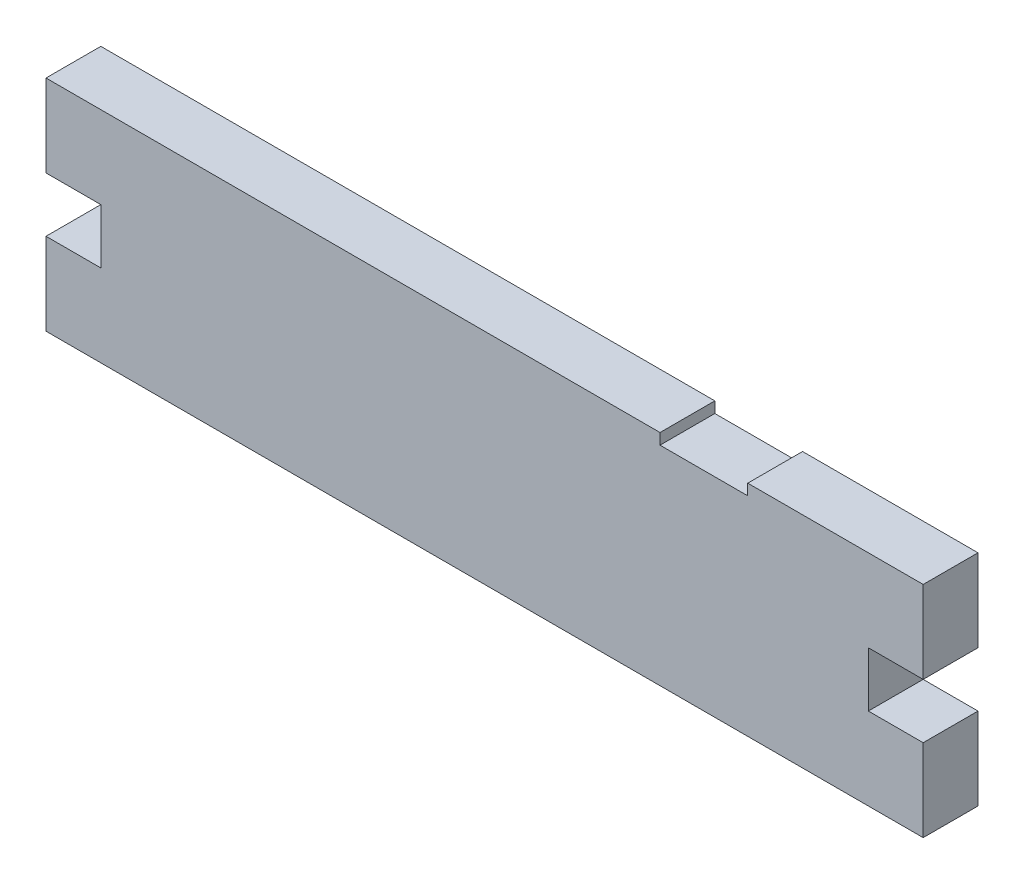
SolidWorks part; units mm, degrees
ref_plane "Plan de face" through (0, 0, 0) normal (0, 0, 1) x (1, 0, 0)
ref_plane "Plan de dessus" through (0, 0, 0) normal (0, 1, 0) x (1, 0, 0)
ref_plane "Plan de droite" through (0, 0, 0) normal (1, 0, 0) x (0, 0, -1)
sketch "Esquisse1" plane through (0, 0, 0) normal (0, 0, 1) x (1, 0, 0)
  line L0 (35, 0) -> (35, 20) construction
  line L1 (0, 0) -> (70, 0)
  line L2 (0, 7.5) -> (0, 12.5)
  line L3 (0, 20) -> (51, 20)
  line L4 (70, 7.5) -> (70, 12.5)
  line L5 (70, 0) -> (75, 0)
  line L6 (0, 20) -> (-5, 20)
  line L7 (59, 20) -> (70, 20)
  line L8 (0, 12.5) -> (-5, 12.5)
  line L9 (-5, 20) -> (-5, 12.5)
  line L10 (0, 0) -> (-5, 0)
  line L12 (0, 7.5) -> (-5, 7.5)
  line L13 (-5, 0) -> (-5, 7.5)
  line L14 (75, 0) -> (75, 7.5)
  line L15 (70, 7.5) -> (75, 7.5)
  line L16 (70, 12.5) -> (75, 12.5)
  line L17 (75, 20) -> (75, 12.5)
  line L18 (70, 20) -> (75, 20)
  line L19 (59, 20) -> (59, 19)
  line L20 (59, 19) -> (51, 19)
  line L21 (51, 20) -> (51, 19)
  dimension "D1" = 70
  dimension "D2" = 20
  dimension "D3" = 11
  dimension "D4" = 7.5
  dimension "D5" = 5
  dimension "D6" = 8
  dimension "D7" = 1
extrude "Boss.-Extru.1" add sketch "Esquisse1" along normal blind 5
